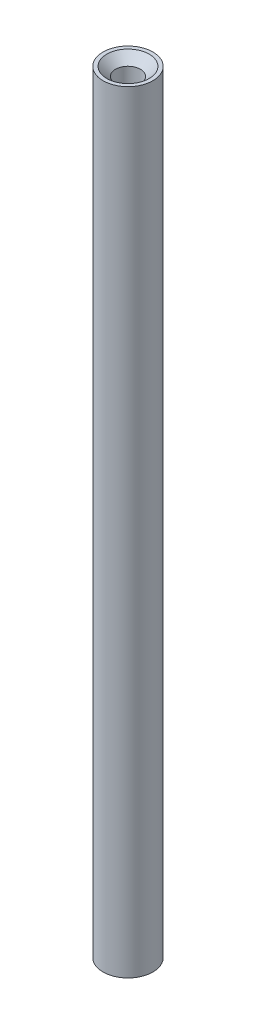
SolidWorks part; units mm, degrees
material "PTFE (general)"
ref_plane "Front" through (0, 0, 0) normal (0, 0, 1) x (1, 0, 0)
ref_plane "Top" through (0, 0, 0) normal (0, 1, 0) x (1, 0, 0)
ref_plane "Right" through (0, 0, 0) normal (1, 0, 0) x (0, 0, -1)
sketch "Sketch1" plane through (0, 0, 0) normal (0, 1, 0) x (1, 0, 0)
  circle A0 centre (0, 0) radius 2
  circle A1 centre (0, 0) radius 1
  dimension "D1" = 2
  dimension "D2" = 4
extrude "Boss-Extrude1" add sketch "Sketch1" along normal blind 62
chamfer "Chamfer1" distance 0.7 angle 45 1 edges at (0, 62, 1)
